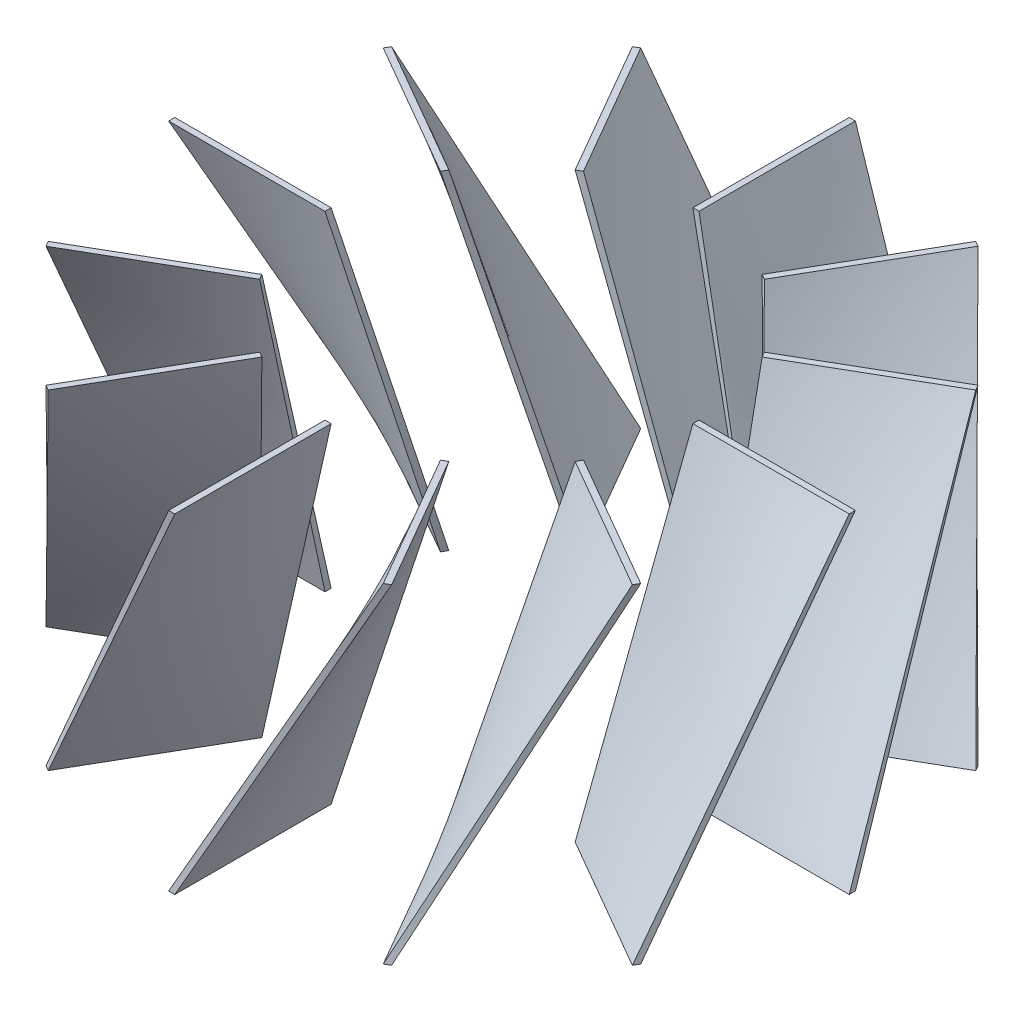
SolidWorks part; units mm, degrees
ref_plane "Front Plane" through (0, 0, 0) normal (0, 0, 1) x (1, 0, 0)
ref_plane "Top Plane" through (0, 0, 0) normal (0, 1, 0) x (1, 0, 0)
ref_plane "Right Plane" through (0, 0, 0) normal (1, 0, 0) x (0, 0, -1)
sketch "Sketch1" plane through (0, 0, 0) normal (0, 1, 0) x (1, 0, 0)
  line L0 (30.4758, 0.508) -> (56.3857, 0.508)
  line L1 (30.4758, -0.508) -> (56.3857, -0.508)
  line L2 (0, 0) -> (30.48, 0) construction
  line L3 (30.4758, 0.508) -> (30.4758, -0.508) construction
  arc A2 (30.4758, -0.508) -> (30.4758, 0.508) centre (0, 0) ccw
  arc A3 (56.3857, -0.508) -> (56.3857, 0.508) centre (0, 0) ccw
  point P8 (61.9389, 2.1494)
  point P10 (30.48, 0)
  point P12 (61.9424, -2.0474)
  dimension "D1" = 30.48
  dimension "D2" = 1.016
  dimension "D3" = 56.388
ref_plane "Plane1" through (0, 54.61, 0) normal (0, 1, 0) x (1, 0, 0)
sketch "Sketch2" plane through (0, 54.61, 0) normal (0, 1, 0) x (1, 0, 0)
  line L0 (0, 0) -> (26.3928, 15.2379) construction
  line L1 (26.1388, 15.6778) -> (26.6468, 14.7979) construction
  line L2 (26.6468, 14.7979) -> (49.0855, 27.7529)
  line L3 (26.1388, 15.6778) -> (48.5775, 28.6328)
  line L4 (0, 0) -> (30.48, 0) construction
  arc A4 (26.6468, 14.7979) -> (26.1388, 15.6778) centre (0, 0) ccw
  arc A5 (49.0855, 27.7529) -> (48.5775, 28.6328) centre (0, 0) ccw
  point P8 (26.3928, 15.2379)
  dimension "D2" = 56.388
  dimension "D3" = 30.48
  dimension "D1" = 1.016
  dimension "D4" = 30
loft "Loft1" add profiles "Sketch1", "Sketch2" connector at (30.4758, 0, 0.508) connector at (26.6468, 54.61, -14.7979)
pattern_circular "CirPattern2" count 12 over 360 about axis through (0, 0, 0) along (0, 1, 0) of bodies 101
